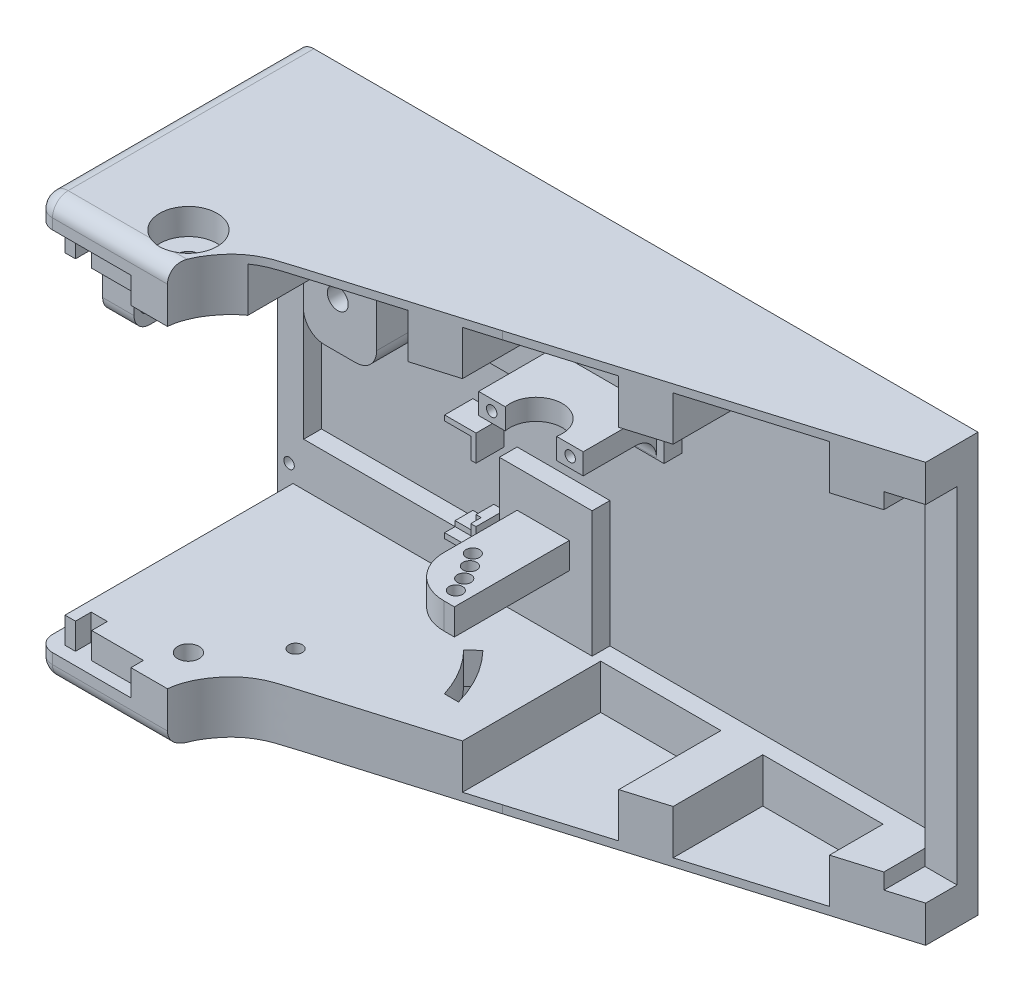
SolidWorks part; units mm, degrees
ref_plane "Front Plane" through (0, 0, 0) normal (0, 0, 1) x (1, 0, 0)
ref_plane "Top Plane" through (0, 0, 0) normal (0, 1, 0) x (1, 0, 0)
ref_plane "Right Plane" through (0, 0, 0) normal (1, 0, 0) x (0, 0, -1)
sketch "Sketch1" plane through (0, 0, 0) normal (0, 0, 1) x (1, 0, 0)
  line L1 (-65, 40) -> (65, 40)
  line L2 (-65, 40) -> (-65, -40)
  line L3 (-65, -40) -> (65, -40)
  line L4 (65, 40) -> (65, -40)
  point P4 (0, 40)
  point P6 (65, 0)
  dimension "D1" = 130
  dimension "D2" = 80
extrude "Extrude1" add sketch "Sketch1" along normal blind 50
sketch "Sketch3" plane through (0, 40, 0) normal (0, 1, 0) x (-1, 0, 0)
  line L0 (-65, 10) -> (40, 41.5) construction
  line L1 (-65, 50) -> (-65, 0) construction
  line L2 (-65, 10) -> (-65, 50)
  line L3 (-65, 50) -> (40, 50)
  line L4 (-65, 50) -> (65, 50) construction
  line L5 (40, 41.5) -> (40, 50) construction
  line L6 (65, 50) -> (65, 0) construction
  line L7 (-2.7241, 28.6828) -> (-65, 10)
  spline S0 degree 3 poles (40, 50) (39.8902, 49.1102) (39.7171, 47.7074) (38.1533, 44.5824) (35.8668, 41.7856) (33.2994, 39.4476) (21.4505, 35.874) (8.4975, 32.0209) (-2.7241, 28.6828) knots 0 0 0 0 0.295315 0.46556 0.498905 0.614331 0.665884 1 1 1 1
  dimension "D1" = 40
  dimension "D2" = 8.5
  dimension "D3" = 25
extrude "Extrude2" cut sketch "Sketch3" against normal blind 110
sketch "Sketch4" plane through (0, 0, 50) normal (0, 0, 1) x (1, 0, 0)
  line L1 (-65, 30) -> (65, 30)
  line L2 (-65, 30) -> (-65, -30)
  line L3 (-65, -30) -> (65, -30)
  line L4 (65, 30) -> (65, -30)
  line L5 (-40, 40) -> (-65, 40) construction
  line L6 (-65, -40) -> (-40, -40) construction
  line L9 (-65, 40) -> (-65, -40) construction
  dimension "D2" = 10
  dimension "D3" = 10
  dimension "D4" = 130
extrude "Extrude3" cut sketch "Sketch4" against normal offset from surface (46 mm away) 4 from offset 0 up to face at (0, 0, 0)
sketch "Sketch7" plane through (0, 0, 50) normal (0, 0, 1) x (1, 0, 0)
  line L0 (-40, 30) -> (-65, 30) construction
  line L1 (-65, 30) -> (-62, 30)
  line L2 (-65, 30) -> (-65, 35)
  line L3 (-65, 35) -> (-62, 35)
  line L4 (-62, 30) -> (-62, 35)
  dimension "D2" = 3
  dimension "D3" = 5
extrude "Extrude6" cut sketch "Sketch7" against normal up to surface (46 mm away) up to face at (0, 0, 4)
sketch "Sketch8" plane through (0, 0, 50) normal (0, 0, 1) x (1, 0, 0)
  line L1 (-62, 35) -> (-47, 35)
  line L2 (-62, 35) -> (-62, 30)
  line L3 (-62, 30) -> (-47, 30)
  line L4 (-47, 35) -> (-47, 30)
  line L5 (-40, 30) -> (-62, 30) construction
  dimension "D1" = 15
extrude "Extrude7" cut sketch "Sketch8" against normal blind 2.4
sketch "Sketch11" plane through (0, -40, 0) normal (0, -1, 0) x (1, 0, 0)
  line L0 (-65, 50) -> (-40, 50) construction
  line L1 (-65, 50) -> (-65, 0) construction
  circle A0 centre (-44, 42) radius 2.05
  dimension "D3" = 4.1
  dimension "D1" = 8
  dimension "D2" = 21
extrude "Extrude9" cut sketch "Sketch11" against normal through all
sketch "Sketch12" plane through (0, 40, 0) normal (0, 1, 0) x (-1, 0, 0)
  circle A0 centre (44, 42) radius 5.5
  dimension "D1" = 11
extrude "Extrude10" cut sketch "Sketch12" against normal blind 5
sketch "Sketch13" plane through (0, 30, 0) normal (0, -1, 0) x (1, 0, 0)
  line L0 (65, 4) -> (65, 10)
  line L1 (65, 10) -> (58.8426, 11.8472)
  line L2 (2.7241, 28.6828) -> (65, 10) construction
  line L3 (58.8426, 11.8472) -> (58.8426, 4)
  line L4 (-62, 4) -> (65, 4) construction
  line L5 (58.8426, 4) -> (65, 4)
extrude "Extrude11" cut sketch "Sketch13" against normal blind 3
mirror "Mirror1" about plane through (0, 0, 0) normal (0, 1, 0) of "Extrude11", "Extrude6", "Extrude7", "Extrude10"
sketch "Sketch15" plane through (0, 0, 4) normal (0, 0, 1) x (1, 0, 0)
  line L1 (-44, 30) -> (-30, 30)
  line L2 (-44, 30) -> (-44, 12)
  line L3 (-44, 12) -> (-30, 12)
  line L4 (-30, 30) -> (-30, 12)
  line L5 (-65, -35) -> (-65, 35) construction
  line L6 (-62, 30) -> (58.8426, 30) construction
  dimension "D1" = 18
  dimension "D2" = 14
  dimension "D4" = 21
extrude "Extrude12" add sketch "Sketch15" along normal blind 16
sketch "Sketch16" plane through (0, 0, 20) normal (0, 0, 1) x (1, 0, 0)
  circle A0 centre (-37.4347, 20.9117) radius 2
  dimension "D1" = 4
extrude "Extrude13" cut sketch "Sketch16" against normal blind 30
sketch "Sketch17" plane through (0, -40, 0) normal (0, -1, 0) x (1, 0, 0)
  circle A0 centre (-34.3954, 31.1146) radius 1.3
  dimension "D1" = 2.6
extrude "Extrude14" cut sketch "Sketch17" against normal blind 10
sketch "Sketch18" plane through (0, -40, 0) normal (0, -1, 0) x (1, 0, 0)
  line L0 (-12.6802, 24.365) -> (-9.9709, 24.365)
  line L1 (-18.0755, 15.279) -> (-16.2095, 13.4684)
  arc A0 (-17.1425, 14.3737) -> (-11.3224, 24.365) centre (-34.3954, 31.1146) ccw construction
  arc A1 (-16.2095, 13.4684) -> (-9.9709, 24.365) centre (-34.3954, 31.1146) ccw
  arc A2 (-18.0755, 15.279) -> (-12.6802, 24.365) centre (-34.3954, 31.1146) ccw
  dimension "D1" = 2.6
  dimension "D2" = 1.3
  dimension "D3" = 48.08
extrude "Extrude15" cut sketch "Sketch18" against normal blind 10
sketch "Sketch19" plane through (0, 0, 4) normal (0, 0, 1) x (1, 0, 0)
  line L0 (58.8426, -30) -> (2.7241, -30) construction
  line L1 (-19.1371, -13) -> (-9.1371, -13)
  line L2 (-19.1371, -13) -> (-19.1371, -18)
  line L3 (-19.1371, -18) -> (-9.1371, -18)
  line L4 (-9.1371, -13) -> (-9.1371, -18)
  dimension "D1" = 12
  dimension "D2" = 5
  dimension "D3" = 10
extrude "Extrude16" add sketch "Sketch19" along normal blind 22
sketch "Sketch21" plane through (0, -18, 0) normal (0, -1, 0) x (1, 0, 0)
  circle A0 centre (-34.3954, 31.1146) radius 22.74 construction
  arc A1 (-18.0755, 15.279) -> (-12.6802, 24.365) centre (-34.3954, 31.1146) ccw construction
  circle A2 centre (-34.3954, 31.1146) radius 25.34 construction
  arc A3 (-16.2095, 13.4684) -> (-9.9709, 24.365) centre (-34.3954, 31.1146) ccw construction
  circle A4 centre (-11.7172, 23.1384) radius 1.3
  circle A5 centre (-12.8872, 20.376) radius 1.3
  circle A6 centre (-14.3921, 17.7808) radius 1.3
  circle A7 centre (-16.2086, 15.3932) radius 1.3
  dimension "D1" = 3
  dimension "D2" = 3
  dimension "D3" = 3
extrude "Extrude17" cut sketch "Sketch21" against normal blind 20
sketch "Sketch22" plane through (0, -40, 0) normal (0, -1, 0) x (1, 0, 0)
  circle A0 centre (-34.3954, 31.1146) radius 3
  dimension "D1" = 6
extrude "Extrude18" cut sketch "Sketch22" against normal blind 4
sketch "Sketch23" plane through (0, -40, 0) normal (0, -1, 0) x (1, 0, 0)
  line L14 (-6.3046, 27.365) -> (-15.0148, 27.365)
  line L15 (-22.4822, 15.3748) -> (-16.2599, 9.3371)
  line L16 (-6.3046, 27.365) -> (-15.0148, 27.365)
  line L17 (-22.4822, 15.3748) -> (-16.2599, 9.3371)
  arc A14 (-16.2599, 9.3371) -> (-6.3046, 27.365) centre (-34.3954, 31.1146) ccw
  arc A15 (-22.4822, 15.3748) -> (-15.0148, 27.365) centre (-34.3954, 31.1146) ccw
  arc A16 (-16.2599, 9.3371) -> (-6.3046, 27.365) centre (-34.3954, 31.1146) ccw
  arc A17 (-22.4822, 15.3748) -> (-15.0148, 27.365) centre (-34.3954, 31.1146) ccw
  dimension "D1" = 3
extrude "Extrude19" cut sketch "Sketch23" against normal blind 4
sketch "Sketch26" plane through (0, 0, 20) normal (0, 0, 1) x (1, 0, 0)
  line L0 (-44, 30) -> (-44, 12) construction
  point P0 (-44, 21)
ref_plane "Plane1" through (0, 21, 0) normal (0, -1, 0) x (1, 0, 0)
fillet "Fillet3" radius 8 1 edges at (-19.1371, -15.5, 26)
fillet "Fillet4" radius 2 4 edges at (-15.0148, -38, 27.365) (-6.3046, -38, 27.365) (-16.2599, -38, 9.3371) (-22.4822, -38, 15.3748)
sketch "Sketch28" plane through (0, 0, 4) normal (0, 0, 1) x (1, 0, 0)
  line L0 (-65, -35) -> (-65, 35) construction
  line L1 (-12.5, 17) -> (7.5, 17)
  line L2 (-12.5, 17) -> (-12.5, 13)
  line L3 (-12.5, 13) -> (7.5, 13)
  line L4 (7.5, 17) -> (7.5, 13)
  line L5 (-30, 30) -> (58.8426, 30) construction
  dimension "D1" = 52.5
  dimension "D2" = 20
  dimension "D3" = 4
  dimension "D4" = 13
extrude "Extrude22" add sketch "Sketch28" along normal blind 14
sketch "Sketch29" plane through (0, 13, 0) normal (0, -1, 0) x (1, 0, 0)
  line L0 (-12.5, 18) -> (7.5, 18) construction
  circle A0 centre (-2.5, 17) radius 5
  point P4 (-2.5, 18)
  point P5 (0, 0)
  dimension "D1" = 10
  dimension "D2" = 1
extrude "Extrude23" cut sketch "Sketch29" against normal blind 8
sketch "Sketch34" plane through (0, 0, 18) normal (0, 0, 1) x (1, 0, 0)
  line L0 (-12.5, 17) -> (-12.5, 13) construction
  line L1 (7.5, 13) -> (7.5, 17) construction
  circle A0 centre (-10, 15) radius 1
  circle A1 centre (5, 15) radius 1
  point P8 (-12.5, 15)
  dimension "D1" = 2
  dimension "D2" = 2.5
  dimension "D3" = 2.5
extrude "Extrude28" cut sketch "Sketch34" against normal blind 10
fillet "Fillet5" radius 4 1 edges at (-2.5, 13, 4)
sketch "Sketch32" plane through (0, 0, 4) normal (0, 0, 1) x (1, 0, 0)
  line L0 (27.8426, 38.5) -> (50.8426, 38.5)
  line L15 (27.8426, 30) -> (50.8426, 30)
  line L16 (27.8426, 30) -> (27.8426, 38.5)
  line L18 (50.8426, 30) -> (50.8426, 38.5)
  dimension "D1" = 8.5
  dimension "D2" = 23
  dimension "D3" = 8
extrude "Extrude26" cut sketch "Sketch32" along normal through all
pattern_linear "LPattern1" count 3 spacing 31 along (-1, 0, 0) of "Extrude26"
mirror "Mirror2" about plane through (0, 0, 0) normal (0, 1, 0) of "Extrude26"
sketch "Sketch33" plane through (0, 0, 4) normal (0, 0, 1) x (1, 0, 0)
  line L0 (27.8426, -30) -> (-62, -30) construction
  line L1 (-3.1574, -30) -> (19.8426, -30)
  line L2 (-3.1574, -30) -> (-3.1574, -38.5)
  line L3 (-3.1574, -38.5) -> (19.8426, -38.5)
  line L4 (19.8426, -30) -> (19.8426, -38.5)
  line L5 (50.8426, -38.5) -> (27.8426, -38.5) construction
  line L6 (19.8426, 30) -> (19.8426, 38.5) construction
  line L7 (-3.1574, 38.5) -> (-3.1574, 30) construction
extrude "Extrude27" cut sketch "Sketch33" along normal through all
sketch "Sketch31" plane through (0, 0, 4) normal (0, 0, 1) x (1, 0, 0)
  line L0 (58.8426, 30) -> (8.9536, 30)
  line L1 (50.8426, 30) -> (58.8426, 30) construction
  line L2 (8.9536, 30) -> (8.9536, 8.7755)
  line L3 (8.9536, 8.7755) -> (-44.1857, 8.7755)
  line L4 (-44.1857, 8.7755) -> (-44.1857, 27.0421)
  line L5 (-44.1857, 27.0421) -> (-59.9547, 27.0421)
  line L6 (-59.9547, 27.0421) -> (-59.9547, -21.6472)
  line L7 (-59.9547, -21.6472) -> (-22.5317, -21.6472)
  line L8 (-22.5317, -21.6472) -> (-22.5317, -5.9214)
  line L9 (-22.5317, -5.9214) -> (-4.7957, -5.9214)
  line L10 (-4.7957, -5.9214) -> (-4.7957, -30)
  line L11 (58.8426, -30) -> (50.8426, -30) construction
  line L12 (-4.7957, -30) -> (58.8426, -30)
  line L13 (58.8426, -30) -> (58.8426, 30)
extrude "Extrude25" cut sketch "Sketch31" against normal blind 3.4
sketch "Sketch35" plane through (0, 0, 0) normal (0, 0, -1) x (-1, 0, 0)
  circle A0 centre (37.4347, 20.9117) radius 5.55
  dimension "D1" = 11.1
extrude "Extrude29" cut sketch "Sketch35" against normal blind 15
fillet "Fillet6" radius 4 3 edges at (-30, 30, 12) (-30, 12, 12) (-44, 12, 12)
sketch "Sketch36" plane through (0, 30, 0) normal (0, 1, 0) x (-1, 0, 0)
  line L1 (56, 46.4) -> (50, 46.4)
  line L2 (56, 35.4) -> (56, 46.4)
  line L3 (56, 35.4) -> (50, 35.4)
  line L4 (50, 46.4) -> (50, 35.4)
  line L5 (62, 47.6) -> (47, 47.6) construction
  line L6 (62, 4) -> (62, 47.6) construction
  dimension "D1" = 1.2
  dimension "D2" = 6
  dimension "D3" = 11
  dimension "D4" = 6
extrude "Extrude30" add sketch "Sketch36" against normal blind 8
sketch "Sketch37" plane through (-56, 0, 0) normal (-1, 0, 0) x (0, 0, 1)
  line L0 (35.4, 22) -> (26.4, 30)
  line L2 (26.4, 30) -> (35.4, 30)
  line L3 (35.4, 30) -> (35.4, 22)
  dimension "D1" = 9
extrude "Extrude31" add sketch "Sketch37" against normal blind 6
sketch "Sketch38" plane through (-56, 0, 0) normal (-1, 0, 0) x (0, 0, 1)
  line L3 (46.4, 22) -> (46.4, 30) construction
  circle A0 centre (43.4, 26) radius 1.95
  circle A1 centre (35.9, 26) radius 1.95
  point P7 (46.4, 26)
  dimension "D1" = 3.9
  dimension "D2" = 3
  dimension "D3" = 7.5
extrude "Extrude32" cut sketch "Sketch38" against normal blind 13
fillet "Fillet7" radius 3 2 edges at (-53, 22, 35.4) (-53, 22, 46.4)
sketch "Sketch40" plane through (0, 0, 0.6) normal (0, 0, 1) x (1, 0, 0)
  line L0 (-62, 35) -> (-62, 30) construction
  line L1 (-25, -2.1472) -> (-31, -2.1472)
  line L2 (-25, -2.1472) -> (-25, -7.1472)
  line L3 (-25, -7.1472) -> (-27, -7.1472)
  line L4 (-31, -2.1472) -> (-31, -4.1472)
  line L5 (-27, -4.1472) -> (-31, -4.1472)
  line L6 (-27, -4.1472) -> (-27, -7.1472)
  line L7 (-26, -3.1472) -> (-62, -3.1472) construction
  line L8 (-26, -3.1472) -> (-26, -21.6472) construction
  line L9 (-26, -21.6472) -> (-62, -21.6472) construction
  line L10 (-62, -3.1472) -> (-62, -21.6472) construction
  line L12 (-25, -22.6472) -> (-31, -22.6472)
  line L13 (-25, -22.6472) -> (-25, -17.6472)
  line L14 (-25, -17.6472) -> (-27, -17.6472)
  line L15 (-31, -22.6472) -> (-31, -20.6472)
  line L16 (-27, -20.6472) -> (-31, -20.6472)
  line L17 (-27, -20.6472) -> (-27, -17.6472)
  line L18 (-59.9547, -21.6472) -> (-22.5317, -21.6472) construction
  point P12 (-31, -3.1472)
  point P13 (-26, -7.1472)
  point P15 (-26, -17.6472)
  point P22 (-31, -21.6472)
  dimension "D1" = 6
  dimension "D2" = 5
  dimension "D3" = 2
  dimension "D4" = 2
  dimension "D5" = 36
  dimension "D6" = 18.5
extrude "Extrude33" add sketch "Sketch40" along normal up to surface (3.4 mm away) up to face at (8.3426, -34.25, 4)
sketch "Sketch41" plane through (0, 0, 4) normal (0, 0, 1) x (1, 0, 0)
  line L0 (-25, -17.6472) -> (-25, -22.6472)
  line L1 (-25, -22.6472) -> (-31, -22.6472)
  line L2 (-31, -22.6472) -> (-31, -21.6472)
  line L4 (-31, -21.6472) -> (-26, -21.6472)
  line L5 (-26, -21.6472) -> (-26, -17.6472)
  line L6 (-25, -17.6472) -> (-27, -17.6472) construction
  line L7 (-25, -7.1472) -> (-25, -2.1472)
  line L8 (-25, -2.1472) -> (-31, -2.1472) construction
  line L9 (-25, -7.1472) -> (-25, -2.1472) construction
  line L10 (-25, -2.1472) -> (-31, -2.1472)
  line L11 (-31, -2.1472) -> (-31, -3.1472)
  line L12 (-31, -2.1472) -> (-31, -4.1472) construction
  line L13 (-31, -3.1472) -> (-26, -3.1472)
  line L14 (-26, -3.1472) -> (-26, -7.1472)
  line L15 (-27, -7.1472) -> (-25, -7.1472) construction
  line L16 (-26, -7.1472) -> (-25, -7.1472)
  line L17 (-25, -17.6472) -> (-26, -17.6472)
  line L19 (-26, -3.1472) -> (-62, -3.1472) construction
  line L20 (-26, -3.1472) -> (-26, -21.6472) construction
  line L21 (-26, -21.6472) -> (-62, -21.6472) construction
  line L22 (-62, -3.1472) -> (-62, -21.6472) construction
  dimension "D1" = 36
  dimension "D2" = 18.5
  dimension "D3" = 1
extrude "Extrude34" add sketch "Sketch41" along normal blind 2
sketch "Sketch43" plane through (0, 0, 47.6) normal (0, 0, 1) x (1, 0, 0)
  line L0 (-62, 30) -> (-47, 30) construction
  line L1 (-56.9, 35) -> (-60, 35)
  line L2 (-56.9, 35) -> (-56.9, 30)
  line L3 (-56.9, 30) -> (-60, 30)
  line L4 (-60, 35) -> (-60, 30)
  line L5 (-47, -35) -> (-62, -35) construction
  line L6 (-56.9, -30) -> (-60, -30)
  line L7 (-56.9, -30) -> (-56.9, -35)
  line L8 (-56.9, -35) -> (-60, -35)
  line L9 (-60, -30) -> (-60, -35)
  line L11 (-62, 35) -> (-62, 30) construction
  line L12 (-62, -30) -> (-47, -30) construction
  dimension "D1" = 3.1
  dimension "D2" = 2
extrude "Extrude35" cut sketch "Sketch43" against normal blind 3
sketch "Sketch44" plane through (0, 0, 4) normal (0, 0, 1) x (1, 0, 0)
  line L0 (-65, -35) -> (-65, 35) construction
  line L1 (-65, 35) -> (-62, 35) construction
  circle A0 centre (-62.75, 27) radius 1
  dimension "D1" = 2
  dimension "D2" = 2.25
  dimension "D3" = 8
extrude "Extrude36" cut sketch "Sketch44" against normal through all
mirror "Mirror3" about plane through (0, 0, 0) normal (0, 1, 0) of "Extrude36"
sketch "Sketch45" plane through (0, 0, 0) normal (0, 0, -1) x (-1, 0, 0)
  circle A0 centre (62.75, 27) radius 1.9
  circle A1 centre (62.75, -27) radius 1.9
  dimension "D1" = 3.8
extrude "Extrude37" cut sketch "Sketch45" against normal blind 2.5
fillet "Fillet8" radius 3 6 edges at (-65, 40, 25) (-65, -37.5, 50) (-65, -40, 25) (-65, 37.5, 50) (-52.5, 40, 50) (-52.5, -40, 50)
sketch "Sketch46" plane through (0, 0, 0) normal (0, 0, -1) x (-1, 0, 0)
  line L0 (-65, 40) -> (62, 40) construction
  line L1 (65, 37) -> (65, -37) construction
  circle A0 centre (55, 37) radius 1.5
  dimension "D1" = 3
  dimension "D2" = 3
  dimension "D3" = 10
extrude "Extrude38" cut sketch "Sketch46" against normal blind 15
pattern_linear "LPattern2" count 2 spacing 79 along (1, 0, 0) count 2 spacing 74 along (0, -1, 0) of "Extrude38"
